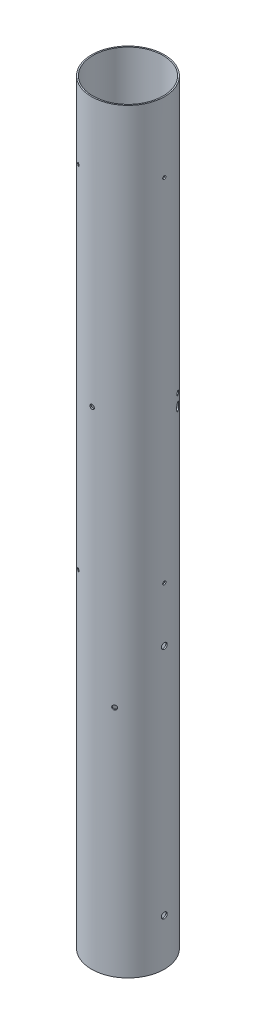
SolidWorks part; units mm, degrees
material "G12 Fiberglass"
ref_plane "Front Plane" through (0, 0, 0) normal (0, 0, 1) x (1, 0, 0)
ref_plane "Top Plane" through (0, 0, 0) normal (0, 1, 0) x (1, 0, 0)
ref_plane "Right Plane" through (0, 0, 0) normal (1, 0, 0) x (0, 0, -1)
sketch "Sketch1" plane through (0, 0, 0) normal (0, 1, 0) x (1, 0, 0)
  circle A0 centre (0, 0) radius 38.227
  circle A1 centre (0, 0) radius 39.624
  dimension "D1" = 76.454
  dimension "D2" = 79.248
extrude "Boss-Extrude1" add sketch "Sketch1" along normal blind 822.5282
ref_axis "Axis1" through (0, -40.64, 0) along (0, 1, 0)
ref_plane "Plane1" through (-19.812, 0, 34.3154) normal (-0.5, 0, 0.866) x (0, -1, 0)
sketch "Sketch2" plane through (-19.812, 0, 34.3154) normal (-0.5, 0, 0.866) x (0, -1, 0)
  line L0 (40.64, 0) -> (-853.44, 0) construction
  line L1 (-822.5282, 38.227) -> (-822.5282, -38.227) construction
  line L2 (-822.5282, 38.227) -> (-822.5282, -38.227) construction
  circle A0 centre (-746.3282, 0) radius 1.778
  dimension "D1" = 76.2
  dimension "D2" = 3.556
extrude "S1A_Coupler" cut sketch "Sketch2" against normal up to next
pattern_circular "S1A_Coupler_Pattern" count 3 over 360 about axis through (0, -40.64, 0) along (0, 1, 0) of "S1A_Coupler"
ref_plane "Plane2" through (39.624, 0, 0) normal (1, 0, 0) x (0, 0, -1)
sketch "Sketch3" plane through (39.624, 0, 0) normal (1, 0, 0) x (0, 0, -1)
  line L0 (0, -40.64) -> (0, 853.44) construction
  circle A0 centre (0, 50.8) radius 3.175
  circle A1 centre (0, 304.8) radius 3.175
  dimension "D1" = 6.35
  dimension "D2" = 6.35
  dimension "D3" = 50.8
  dimension "D4" = 254
extrude "S1A_Rail_Guide" cut sketch "Sketch3" against normal up to next
ref_plane "Plane3" through (0, 530.4282, 0) normal (0, 1, 0) x (1, 0, 0)
ref_axis "Axis2" through (-19.2315, 746.3282, 33.3099) along (-0.5, 0, 0.866)
ref_plane "Plane4" through (-34.592, 0, -19.3249) normal (-0.873, 0, -0.4877) x (0, -1, 0)
sketch "Sketch4" plane through (-34.592, 0, -19.3249) normal (-0.873, 0, -0.4877) x (0, -1, 0)
  line L0 (-530.4282, 43.8379) -> (-530.4282, -43.8379) construction
  line L1 (40.64, 0) -> (-853.44, 0) construction
  circle A0 centre (-530.4282, 0) radius 2.3812
  dimension "D1" = 4.7625
extrude "S1A_Pressure" cut sketch "Sketch4" against normal up to next
pattern_circular "S1A_Pressure_Pattern" count 3 over 360 about axis through (0, -40.64, 0) along (0, 1, 0) of "S1A_Pressure"
ref_plane "Plane5" through (0, 511.3782, 0) normal (0, 1, 0) x (1, 0, 0)
ref_plane "Plane6" through (34.0319, 0, -20.2951) normal (0.8589, 0, -0.5122) x (0, -1, 0)
sketch "Sketch6" plane through (34.0319, 0, -20.2951) normal (0.8589, 0, -0.5122) x (0, -1, 0)
  line L0 (-518.9982, 0) -> (-516.4582, 0) construction
  line L1 (-518.9982, 3.175) -> (-516.4582, 3.175)
  line L2 (-518.9982, -3.175) -> (-516.4582, -3.175)
  line L3 (-822.5282, 0) -> (0, 0) construction
  line L4 (-822.5282, 39.624) -> (-822.5282, -39.624) construction
  arc A0 (-518.9982, 3.175) -> (-518.9982, -3.175) centre (-518.9982, 0) ccw
  arc A1 (-516.4582, -3.175) -> (-516.4582, 3.175) centre (-516.4582, 0) ccw
  point P1 (-517.7282, 0)
  dimension "D1" = 2.54
  dimension "D2" = 3.175
  dimension "D3" = 304.8
extrude "Switch_Slot" cut sketch "Sketch6" against normal up to next
ref_plane "Plane7" through (0, 254, 0) normal (0, 1, 0) x (1, 0, 0)
ref_plane "Plane8" through (19.812, 0, 34.3154) normal (0.5, 0, 0.866) x (0, -1, 0)
sketch "Sketch7" plane through (19.812, 0, 34.3154) normal (0.5, 0, 0.866) x (0, -1, 0)
  line L0 (-254, 43.8379) -> (-254, -43.8379) construction
  circle A0 centre (-254, 0) radius 2.3813
  dimension "D1" = 4.7625
extrude "S1A_Pressure_2" cut sketch "Sketch7" against normal up to next
pattern_circular "S1A_Pressure_2_Pattern" count 3 over 360 about axis through (0, -40.64, 0) along (0, 1, 0) of "S1A_Pressure_2"
sketch "Sketch8" plane through (-19.812, 0, 34.3154) normal (-0.5, 0, 0.866) x (0, -1, 0)
  circle A0 centre (-364.1217, 0) radius 1.7859
  dimension "D1" = 3.5719
  dimension "D2" = 364.1217
extrude "S1B_Propulsion_Bulkhead" cut sketch "Sketch8" against normal up to next
pattern_circular "S1B_Propulsion_Bulkhead_Pattern" count 3 over 360 about axis through (0, -40.64, 0) along (0, 1, 0) of "S1B_Propulsion_Bulkhead"
ref_plane "Plane9" through (0, 0, 39.624) normal (0, 0, 1) x (1, 0, 0)
ref_plane "Plane10" through (0, 0, 0) normal (0.866, 0, -0.5) x (0, 1, 0)
equation "\"D2@Sketch3\"=\"D1@Sketch3\""
